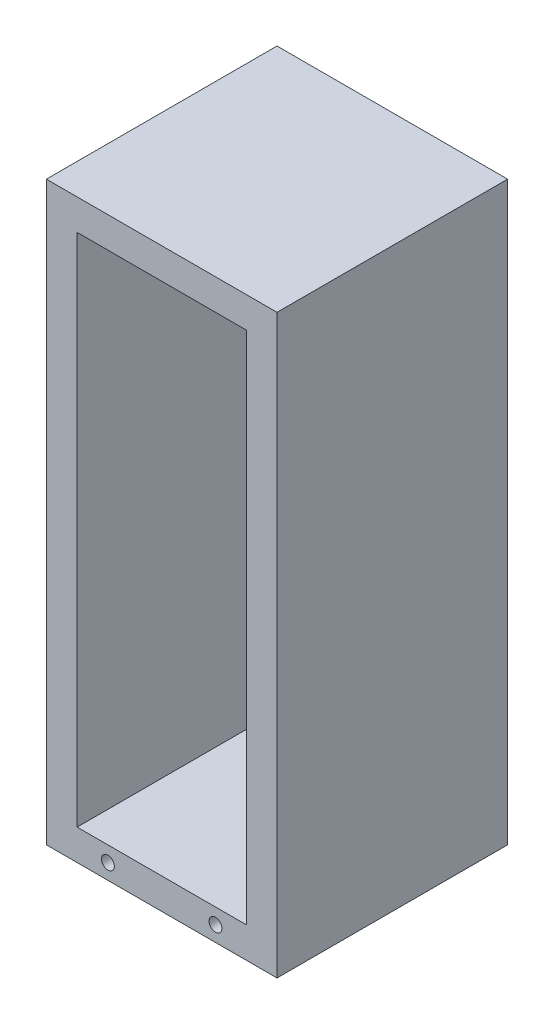
SolidWorks part; units mm, degrees
ref_plane "Front Plane" through (0, 0, 0) normal (0, 0, 1) x (1, 0, 0)
ref_plane "Top Plane" through (0, 0, 0) normal (0, 1, 0) x (1, 0, 0)
ref_plane "Right Plane" through (0, 0, 0) normal (1, 0, 0) x (0, 0, -1)
sketch "Sketch1" plane through (0, 0, 0) normal (0, 0, 1) x (1, 0, 0)
  line L1 (0, 0) -> (75, 0)
  line L2 (0, 0) -> (0, 187.5)
  line L3 (0, 187.5) -> (75, 187.5)
  line L4 (75, 0) -> (75, 187.5)
  line L5 (10, 10) -> (65, 10)
  line L6 (10, 10) -> (10, 177.5)
  line L7 (10, 177.5) -> (65, 177.5)
  line L8 (65, 10) -> (65, 177.5)
  dimension "D1" = 75
  dimension "D2" = 187.5
  dimension "D3" = 10
  dimension "D4" = 10
  dimension "D5" = 10
  dimension "D6" = 10
extrude "Boss-Extrude1" add sketch "Sketch1" against normal blind 75
sketch "Sketch2" plane through (0, 0, 0) normal (0, 0, 1) x (1, 0, 0)
  line L0 (0, 5) -> (75, 5) construction
  line L3 (10, 10) -> (65, 10) construction
  line L4 (37.5, 10) -> (37.5, 0) construction
  line L5 (0, 0) -> (75, 0) construction
  line L8 (0, 187.5) -> (0, 0) construction
  line L9 (75, 0) -> (75, 187.5) construction
  circle A0 centre (20, 5) radius 2
  circle A1 centre (55, 5) radius 2
  dimension "D3" = 4
  dimension "D1" = 5
  dimension "D2" = 17.5
ref_plane "Plane1" through (0, 0, -37.5) normal (0, 0, 1) x (1, 0, 0)
hole_wizard "Tap Drill for M5x0.8 Tap1" positions "Sketch3" profile "Sketch4" hole size "M5x0.8" standard "ANSI Metric"
sketch "Sketch3" plane through (0, 0, 0) normal (0, 0, 1) x (1, 0, 0)
  point P0 (20, 5)
  point P3 (55, 5)
sketch "Sketch4" plane through (20, 5, 0) normal (1, 0, 0) x (0, -1, 0)
  line L0 (0, 0) -> (0, 8.9618)
  line L1 (0, 8.9618) -> (2.1, 7.7)
  line L2 (2.1, 7.7) -> (2.1, 0)
  line L5 (2.1, 0) -> (0, 0)
  line L10 (0, 8.9618) -> (-2.1, 7.7) construction
  line L11 (0, -6.35) -> (0, 107.95) construction
  dimension "Hole Dia." = 4.2
  dimension "Hole Depth" = 7.7
  dimension "Drill Angle" = 118
mirror "Mirror1" about plane through (0, 0, -37.5) normal (0, 0, 1) of "Tap Drill for M5x0.8 Tap1"
hole_wizard "Tap Drill for M5x0.8 Tap2" positions "Sketch8" profile "Sketch9" hole size "M5x0.8" standard "ANSI Metric" end condition through all
sketch "Sketch8" plane through (0, 10, 0) normal (0, 1, 0) x (1, 0, 0)
  line L0 (37.5, 75) -> (37.5, 0) construction
  line L1 (10, 75) -> (65, 75) construction
  line L2 (10, 0) -> (65, 0) construction
  point P0 (37.5, 37.5)
sketch "Sketch9" plane through (37.5, 10, -37.5) normal (1, 0, 0) x (0, 0, 1)
  line L0 (0, 0) -> (0, 10)
  line L1 (0, 10) -> (2.1, 10)
  line L2 (2.1, 10) -> (2.1, 0)
  line L5 (2.1, 0) -> (0, 0)
  line L11 (0, -6.35) -> (0, 107.95) construction
  dimension "Thru Hole Dia." = 4.2
  dimension "Thru Hole Depth" = 10
